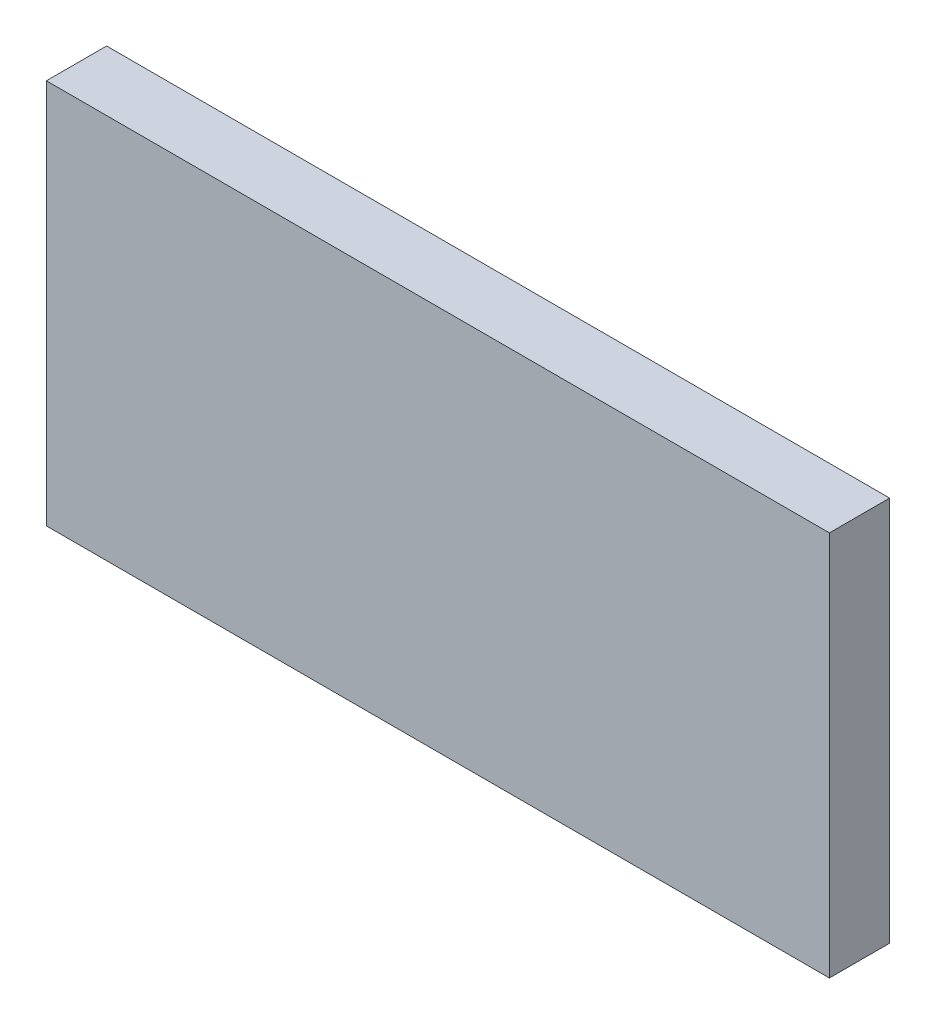
SolidWorks part; units mm, degrees
ref_plane "Front Plane" through (0, 0, 0) normal (0, 0, 1) x (1, 0, 0)
ref_plane "Top Plane" through (0, 0, 0) normal (0, 1, 0) x (1, 0, 0)
ref_plane "Right Plane" through (0, 0, 0) normal (1, 0, 0) x (0, 0, -1)
sketch "Sketch1" plane through (0, 0, 0) normal (0, 0, 1) x (1, 0, 0)
  line L1 (-7.5, 10) -> (7.5, 10)
  line L2 (-7.5, 10) -> (-7.5, -10)
  line L3 (-7.5, -10) -> (7.5, -10)
  line L4 (7.5, 10) -> (7.5, -10)
  line L5 (-7.5, 10) -> (7.5, -10) construction
  line L6 (-7.5, -10) -> (7.5, 10) construction
  point P0 (0, 0)
  dimension "D1" = 15
  dimension "D2" = 20
extrude "Boss-Extrude1" add sketch "Sketch1" along normal blind 230
sketch "Sketch2" plane through (0, 0, 0) normal (0, 0, -1) x (-1, 0, 0)
  line L1 (-32.5, 10) -> (32.5, 10)
  line L2 (-32.5, 10) -> (-32.5, 50)
  line L3 (-32.5, 50) -> (32.5, 50)
  line L4 (32.5, 10) -> (32.5, 50)
  line L6 (-7.5, 10) -> (7.5, 10) construction
  point P4 (0, 10)
  point P10 (0, 10)
  dimension "D1" = 65
  dimension "D2" = 40
extrude "Boss-Extrude6" add sketch "Sketch2" against normal blind 5 separate body
sketch "Sketch7" plane through (32.5, 0, 0) normal (1, 0, 0) x (0, 0, -1)
  line L0 (0, 50) -> (0, 10) construction
  line L1 (0, 37.5) -> (-75, 37.5)
  line L2 (0, 37.5) -> (0, 22.5)
  line L3 (0, 22.5) -> (-75, 22.5)
  line L4 (-75, 37.5) -> (-75, 22.5)
  point P4 (0, 30)
  point P7 (0, 30)
  dimension "D1" = 15
  dimension "D2" = 75
extrude "Boss-Extrude7" add sketch "Sketch7" along normal blind 5 separate body
sketch "Sketch8" plane through (-32.5, 0, 0) normal (-1, 0, 0) x (0, 0, 1)
  line L1 (0, 37.5) -> (75, 37.5)
  line L2 (0, 37.5) -> (0, 22.5)
  line L3 (0, 22.5) -> (75, 22.5)
  line L4 (75, 37.5) -> (75, 22.5)
extrude "Boss-Extrude8" add sketch "Sketch8" along normal blind 5 separate body
sketch "Sketch9" plane through (0, 0, 75) normal (0, 0, 1) x (1, 0, 0)
  line L1 (-32.5, 42) -> (32.5, 42)
  line L2 (-32.5, 42) -> (-32.5, 10)
  line L3 (-32.5, 10) -> (32.5, 10)
  line L4 (32.5, 42) -> (32.5, 10)
  dimension "D1" = 32
extrude "Boss-Extrude11" add sketch "Sketch9" against normal blind 5 separate body
sketch "Sketch10" plane through (-7.5, 0, 0) normal (-1, 0, 0) x (0, 0, 1)
  line L0 (230, 10) -> (230, -10) construction
  line L2 (209.8431, 2) -> (211.3431, 2)
  line L3 (209.8431, 2) -> (209.8431, -2)
  line L4 (209.8431, -2) -> (211.3431, -2)
  line L6 (209.8431, 2) -> (211, 0) construction
  line L7 (209.8431, -2) -> (211, 0) construction
  arc A0 (211.3431, -2) -> (211.3431, 2) centre (217, 0) ccw
  point P4 (230, 0)
  point P5 (211, 0)
  point P11 (209.8431, 0)
  dimension "D1" = 12
  dimension "D2" = 13
  dimension "D3" = 1.5
  dimension "D4" = 4
extrude "Cut-Extrude1" cut sketch "Sketch10" against normal through all
delete or keep bodies "Body-Delete/Keep 3" type delete bodies bodies 106 107 108 110
